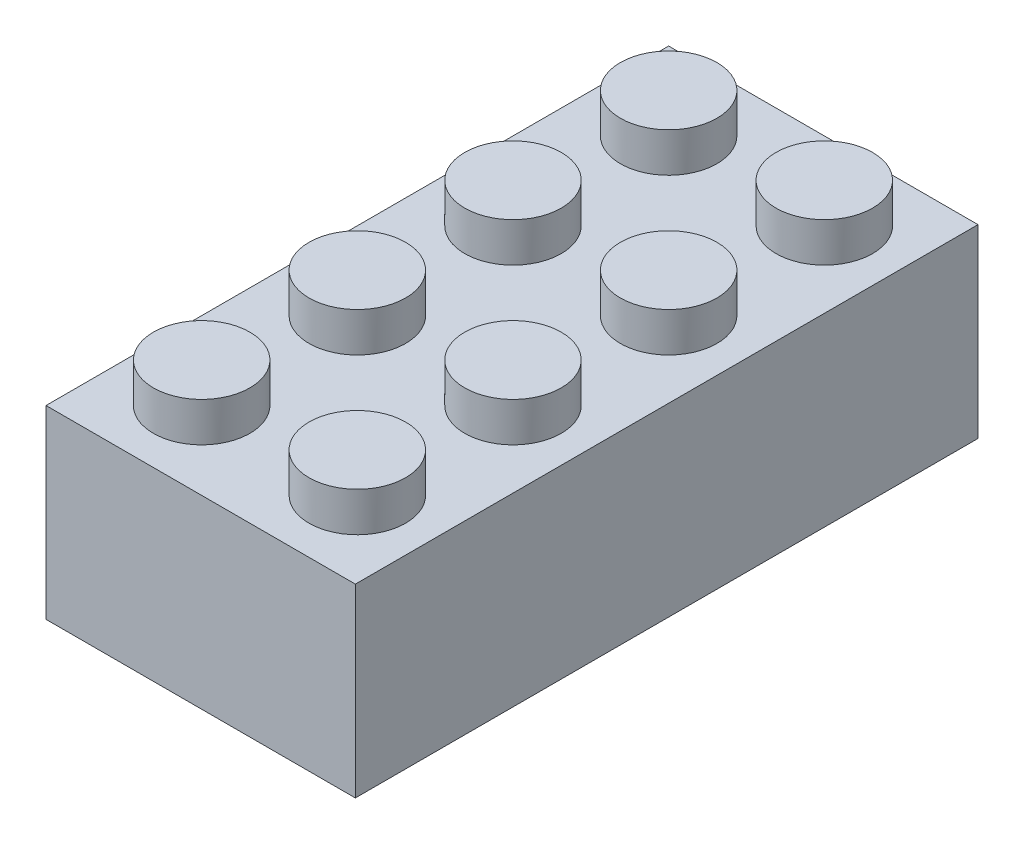
SolidWorks part; units mm, degrees
ref_plane "Front Plane" through (0, 0, 0) normal (0, 0, 1) x (1, 0, 0)
ref_plane "Top Plane" through (0, 0, 0) normal (0, 1, 0) x (1, 0, 0)
ref_plane "Right Plane" through (0, 0, 0) normal (1, 0, 0) x (0, 0, -1)
sketch "stencil" plane through (0, 0, 0) normal (0, 1, 0) x (1, 0, 0)
  line L2 (0, 0) -> (0, 31.5) construction
  line L29 (0, 0) -> (15.7, 0) construction
  line L30 (0, 3.95) -> (15.7, 3.95) construction
  line L31 (0, 7.9) -> (15.7, 7.9) construction
  line L32 (0, 11.85) -> (15.7, 11.85) construction
  line L33 (0, 15.8) -> (15.7, 15.8) construction
  line L34 (0, 19.75) -> (15.7, 19.75) construction
  line L35 (0, 23.7) -> (15.7, 23.7) construction
  line L36 (0, 27.65) -> (15.7, 27.65) construction
  line L37 (0, 31.6) -> (15.7, 31.6) construction
  line L38 (3.95, 0) -> (3.95, 31.5) construction
  line L39 (7.9, 0) -> (7.9, 31.5) construction
  line L40 (11.85, 0) -> (11.85, 31.5) construction
  line L41 (15.8, 0) -> (15.8, 31.5) construction
  line L42 (0, 31.6) -> (0, 0)
  line L43 (0, 0) -> (15.7, 0)
  line L44 (15.7, 0) -> (15.8, 31.5)
  line L45 (15.8, 31.5) -> (0, 31.5)
  circle A26 centre (3.95, 3.95) radius 2.45
  circle A27 centre (11.85, 3.95) radius 2.45
  circle A28 centre (11.85, 11.85) radius 2.45
  circle A29 centre (3.95, 11.85) radius 2.45
  circle A30 centre (11.85, 19.75) radius 2.45
  circle A31 centre (3.95, 19.75) radius 2.45
  circle A32 centre (11.85, 27.65) radius 2.45
  circle A33 centre (3.95, 27.65) radius 2.45
  circle A34 centre (7.85, 7.9) radius 3.2
  circle A35 centre (7.85, 7.9) radius 2.4
  circle A36 centre (7.85, 15.8) radius 2.4
  circle A37 centre (7.85, 15.8) radius 3.2
  circle A38 centre (7.85, 23.7) radius 2.4
  circle A39 centre (7.85, 23.7) radius 3.2
  point P6 (3.95, -15.8)
  point P9 (7.9, -15.8)
  point P10 (7.9, -11.85)
  point P13 (3.95, -7.9)
  point P15 (7.9, -7.9)
  point P17 (7.9, -3.95)
  point P18 (3.95, 0)
  point P21 (7.9, 0)
  point P25 (7.9, 3.95)
  point P27 (3.95, 7.9)
  point P28 (7.9, 7.9)
  point P29 (0, -11.85)
  point P30 (0, -7.9)
  point P31 (0, 3.95)
  point P34 (0, -3.95)
  point P36 (0, 15.8)
  point P37 (0, 23.7)
  point P38 (7.9, 23.7)
  point P39 (15.8, 23.7)
  point P40 (15.8, 15.8)
  point P41 (15.8, 7.9)
  dimension "D7" = 4.9
  dimension "D9" = 6.4
  dimension "D1" = 31.5
  dimension "D2" = 15.7
  dimension "D4" = 3.95
  dimension "D6" = 3.95
  dimension "D8" = 0.8
  dimension "D5" = 9
  dimension "D3" = 5
sketch "Sketch1" plane through (0, 0, 0) normal (0, 1, 0) x (1, 0, 0)
  line L17 (0, 0) -> (15.7, 0)
  line L18 (0, 0) -> (0, 31.6)
  line L19 (0, 31.6) -> (15.7, 31.6)
  line L20 (15.7, 0) -> (15.7, 31.6)
extrude "Boss-Extrude1" add sketch "Sketch1" along normal mid plane 9.4
sketch "Sketch2" plane through (0, 4.7, 0) normal (0, 1, 0) x (1, 0, 0)
  circle A3 centre (3.95, 3.95) radius 2.45
  circle A11 centre (11.85, 3.95) radius 2.45
  circle A12 centre (11.85, 11.85) radius 2.45
  circle A13 centre (3.95, 11.85) radius 2.45
  circle A14 centre (3.95, 19.75) radius 2.45
  circle A15 centre (11.85, 19.75) radius 2.45
  circle A16 centre (3.95, 27.65) radius 2.45
  circle A26 centre (3.95, 27.65) radius 2.45 construction
  circle A27 centre (11.85, 27.65) radius 2.45
extrude "Boss-Extrude2" add sketch "Sketch2" along normal blind 2
sketch "Sketch3" plane through (0, -4.7, 0) normal (0, -1, 0) x (1, 0, 0)
  line L0 (0, -15.8) -> (15.7, -15.8) construction
  line L5 (14.3, -30.2) -> (1.4, -30.2)
  line L7 (14.3, -30.2) -> (14.3, -1.4)
  line L15 (14.3, -1.4) -> (1.4, -1.4)
  line L16 (1.4, -30.2) -> (1.4, -1.4)
  line L17 (7.85, -1.4) -> (7.85, -30.2) construction
  line L18 (14.3, -15.8) -> (1.4, -15.8) construction
  line L19 (0, 0) -> (15.7, 0) construction
  line L20 (0, -31.6) -> (0, 0) construction
  point P0 (7.85, -15.8)
  dimension "D1" = 1.4
  dimension "D2" = 1.4
extrude "Cut-Extrude1" cut sketch "Sketch3" against normal blind 4
sketch "Sketch4" plane through (0, -0.7, 0) normal (0, -1, 0) x (1, 0, 0)
  line L0 (0, -7.9) -> (15.7, -7.9) construction
  line L1 (0, -15.8) -> (15.7, -15.8) construction
  line L2 (0, -23.7) -> (15.7, -23.7) construction
  circle A2 centre (7.85, -7.9) radius 3.2
  circle A3 centre (7.85, -7.9) radius 2.4
  circle A6 centre (7.85, -15.8) radius 3.2
  circle A7 centre (7.85, -15.8) radius 2.4
  circle A10 centre (7.85, -23.7) radius 3.2
  circle A11 centre (7.85, -23.7) radius 2.4
  circle A20 centre (7.85, -23.7) radius 2.4 construction
  circle A21 centre (7.85, -23.7) radius 3.2 construction
extrude "Boss-Extrude3" add sketch "Sketch4" along normal up to surface (4 mm away) up to face at (7.85, -4.7, -15.8)
equation "\"t\"= 0.10'tolerance"
equation "\"D1@Sketch3\"= 1.5 - \"t\""
equation "\"D2@Sketch3\"=1.5-\"t\""
equation "\"D1@stencil\"=31.60mm-\"t\""
equation "\"D9@stencil\"=6.5-\"t\""
equation "\"D2@stencil\"=15.80-\"t\""
equation "\"D1@Boss-Extrude1\"=9.5-\"t\""
